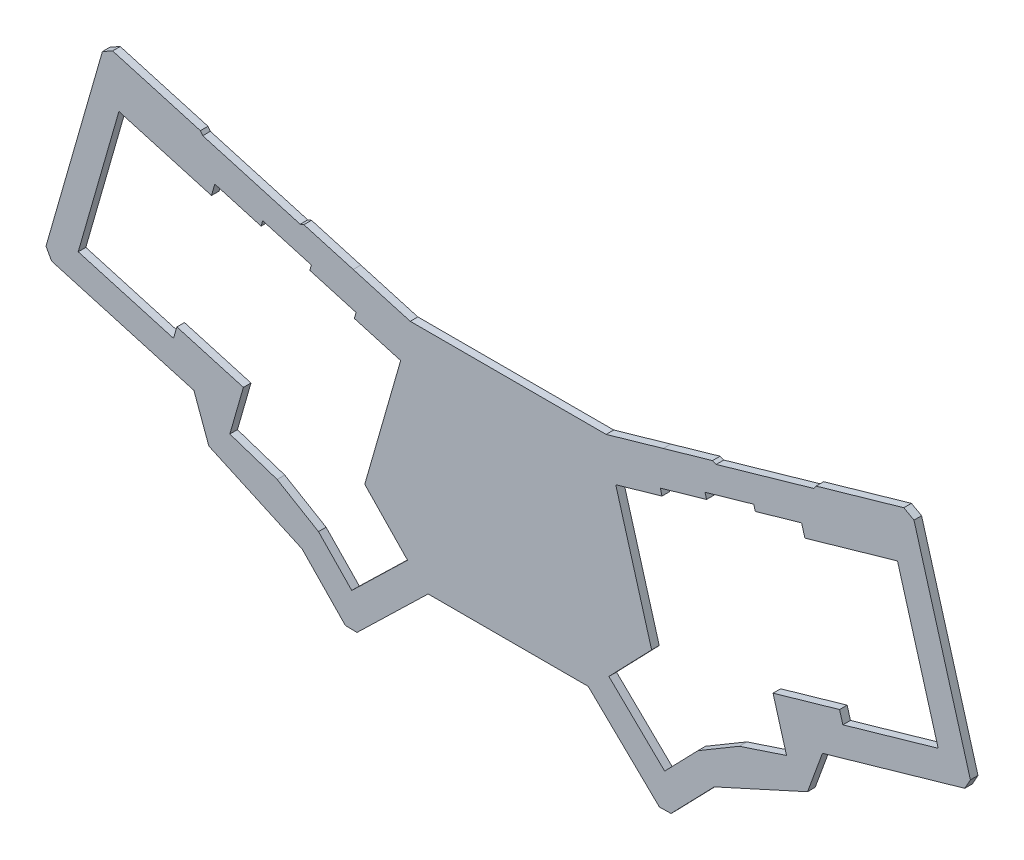
SolidWorks part; units mm, degrees
ref_plane "Plan de face" through (0, 0, 0) normal (0, 0, 1) x (1, 0, 0)
ref_plane "Plan de dessus" through (0, 0, 0) normal (0, 1, 0) x (1, 0, 0)
ref_plane "Plan de droite" through (0, 0, 0) normal (1, 0, 0) x (0, 0, -1)
sketch "Esquisse1" plane through (0, 0, 0) normal (0, 0, 1) x (1, 0, 0)
  line L0 (-121.6461, -32.0475) -> (-108.1875, -28.1884) construction
  line L1 (-108.1875, -28.1884) -> (-104.3283, -41.647) construction
  line L2 (-104.3283, -41.647) -> (-117.7869, -45.5062) construction
  line L3 (-117.7869, -45.5062) -> (-121.6461, -32.0475) construction
  line L4 (-100.1763, -37.9855) -> (-104.0355, -24.5269) construction
  line L5 (-104.0355, -24.5269) -> (-90.5769, -20.6677) construction
  line L6 (-90.5769, -20.6677) -> (-86.7177, -34.1263) construction
  line L7 (-86.7177, -34.1263) -> (-100.1763, -37.9855) construction
  line L8 (-82.5657, -30.4649) -> (-86.4249, -17.0063) construction
  line L9 (-86.4249, -17.0063) -> (-72.9663, -13.1471) construction
  line L10 (-72.9663, -13.1471) -> (-69.1071, -26.6057) construction
  line L11 (-69.1071, -26.6057) -> (-82.5657, -30.4649) construction
  line L12 (-63.6458, -27.5106) -> (-67.505, -14.0519) construction
  line L13 (-67.505, -14.0519) -> (-54.0463, -10.1927) construction
  line L14 (-54.0463, -10.1927) -> (-50.1872, -23.6514) construction
  line L15 (-50.1872, -23.6514) -> (-63.6458, -27.5106) construction
  line L16 (-44.0711, -26.8394) -> (-47.9303, -13.3808) construction
  line L17 (-47.9303, -13.3808) -> (-34.4717, -9.5216) construction
  line L18 (-34.4717, -9.5216) -> (-30.6125, -22.9802) construction
  line L19 (-30.6125, -22.9802) -> (-44.0711, -26.8394) construction
  line L20 (-25.8054, -21.6018) -> (-29.6646, -8.1432) construction
  line L21 (-29.6646, -8.1432) -> (-16.206, -4.284) construction
  line L22 (-16.206, -4.284) -> (-12.3468, -17.7426) construction
  line L23 (-12.3468, -17.7426) -> (-25.8054, -21.6018) construction
  line L24 (-116.4086, -50.3128) -> (-102.95, -46.4536) construction
  line L25 (-102.95, -46.4536) -> (-99.0908, -59.9122) construction
  line L26 (-99.0908, -59.9122) -> (-112.5494, -63.7714) construction
  line L27 (-112.5494, -63.7714) -> (-116.4086, -50.3128) construction
  line L28 (-98.798, -42.7922) -> (-85.3394, -38.933) construction
  line L29 (-85.3394, -38.933) -> (-81.4802, -52.3916) construction
  line L30 (-81.4802, -52.3916) -> (-94.9388, -56.2508) construction
  line L31 (-94.9388, -56.2508) -> (-98.798, -42.7922) construction
  line L32 (-81.1874, -35.2715) -> (-67.7288, -31.4123) construction
  line L33 (-67.7288, -31.4123) -> (-63.8696, -44.8709) construction
  line L34 (-63.8696, -44.8709) -> (-77.3282, -48.7301) construction
  line L35 (-77.3282, -48.7301) -> (-81.1874, -35.2715) construction
  line L36 (-62.2675, -32.3172) -> (-48.8089, -28.458) construction
  line L37 (-48.8089, -28.458) -> (-44.9497, -41.9166) construction
  line L38 (-44.9497, -41.9166) -> (-58.4083, -45.7758) construction
  line L39 (-58.4083, -45.7758) -> (-62.2675, -32.3172) construction
  line L40 (-42.6928, -31.646) -> (-29.2342, -27.7869) construction
  line L41 (-29.2342, -27.7869) -> (-25.375, -41.2455) construction
  line L42 (-25.375, -41.2455) -> (-38.8336, -45.1047) construction
  line L43 (-38.8336, -45.1047) -> (-42.6928, -31.646) construction
  line L44 (-24.4271, -26.4084) -> (-10.9685, -22.5492) construction
  line L45 (-10.9685, -22.5492) -> (-7.1093, -36.0078) construction
  line L46 (-7.1093, -36.0078) -> (-20.5679, -39.867) construction
  line L47 (-20.5679, -39.867) -> (-24.4271, -26.4084) construction
  line L48 (-19.1896, -44.6737) -> (-5.731, -40.8145) construction
  line L49 (-5.731, -40.8145) -> (-1.8718, -54.2731) construction
  line L50 (-1.8718, -54.2731) -> (-15.3304, -58.1323) construction
  line L51 (-15.3304, -58.1323) -> (-19.1896, -44.6737) construction
  line L52 (-37.4554, -49.9113) -> (-23.9967, -46.0521) construction
  line L53 (-23.9967, -46.0521) -> (-20.1376, -59.5107) construction
  line L54 (-20.1376, -59.5107) -> (-33.5962, -63.3699) construction
  line L55 (-33.5962, -63.3699) -> (-37.4554, -49.9113) construction
  line L56 (-57.03, -50.5825) -> (-43.5714, -46.7233) construction
  line L57 (-43.5714, -46.7233) -> (-39.7122, -60.1819) construction
  line L58 (-39.7122, -60.1819) -> (-53.1708, -64.0411) construction
  line L59 (-53.1708, -64.0411) -> (-57.03, -50.5825) construction
  line L60 (-75.9499, -53.5368) -> (-62.4913, -49.6776) construction
  line L61 (-62.4913, -49.6776) -> (-58.6321, -63.1362) construction
  line L62 (-58.6321, -63.1362) -> (-72.0908, -66.9954) construction
  line L63 (-72.0908, -66.9954) -> (-75.9499, -53.5368) construction
  line L64 (-93.5605, -61.0574) -> (-80.1019, -57.1982) construction
  line L65 (-80.1019, -57.1982) -> (-76.2427, -70.6569) construction
  line L66 (-76.2427, -70.6569) -> (-89.7013, -74.516) construction
  line L67 (-89.7013, -74.516) -> (-93.5605, -61.0574) construction
  line L68 (-111.1711, -68.5781) -> (-97.7125, -64.7189) construction
  line L69 (-97.7125, -64.7189) -> (-93.8533, -78.1775) construction
  line L70 (-93.8533, -78.1775) -> (-107.3119, -82.0367) construction
  line L71 (-107.3119, -82.0367) -> (-111.1711, -68.5781) construction
  line L72 (-79.0181, -77.3048) -> (-65.5595, -73.4456) construction
  line L73 (-65.5595, -73.4456) -> (-61.7003, -86.9042) construction
  line L74 (-61.7003, -86.9042) -> (-75.1589, -90.7634) construction
  line L75 (-75.1589, -90.7634) -> (-79.0181, -77.3048) construction
  line L76 (-99.4001, -88.1351) -> (-87.3916, -80.9362)
  line L77 (-87.3916, -80.9362) -> (-80.1927, -92.9448)
  line L78 (-80.1927, -92.9448) -> (-92.2012, -100.1436)
  line L79 (-92.2012, -100.1436) -> (-99.4001, -88.1351)
  line L80 (-120.0498, -100.4367) -> (-110.317, -90.3719)
  line L81 (-110.317, -90.3719) -> (-100.2522, -100.1047)
  line L82 (-100.2522, -100.1047) -> (-109.985, -110.1695)
  line L83 (-109.985, -110.1695) -> (-120.0498, -100.4367)
  line L86 (0.634, -55.7756) -> (-52.9527, -71.1413) construction
  line L89 (-59.2205, -88.2424) -> (-52.9527, -71.1413) construction
  line L96 (-93.4066, -103.0586) -> (-59.4637, -88.3612) construction
  line L97 (-105.418, -115.2057) -> (-93.9754, -103.3509) construction
  line L98 (-126.5332, -96.9919) -> (-107.5003, -115.385) construction
  line L99 (-167.7972, -50.1766) -> (-183.2082, -64.014) construction
  line L100 (-106.3822, -25.4572) -> (-123.6848, -30.4187) construction
  line L101 (-72.1178, -10.6906) -> (-88.4663, -15.3784) construction
  line L102 (-53.2337, -7.6163) -> (-70.5393, -12.5786) construction
  line L103 (-33.6604, -6.9452) -> (-50.9661, -11.9075) construction
  line L104 (-15.3965, -1.7081) -> (-31.745, -6.396) construction
  line L105 (0.5403, -55.2132) -> (-14.6896, -2.0999) construction
  line L106 (-16.199, -60.6113) -> (0.1495, -55.9235) construction
  line L107 (-52.7198, -71.0835) -> (-18.1144, -61.1606) construction
  line L108 (-59.1184, -88.0534) -> (-52.9674, -71.2752) construction
  line L109 (-183.2082, -64.014) -> (-173.1824, -64.9357) construction
  line L113 (-102.2678, -134.438) -> (-84.7238, -116.3191) construction
  line L114 (-84.7238, -116.3191) -> (-47.2969, -99.2981) construction
  line L115 (-47.2969, -99.2981) -> (-41.4917, -83.4594) construction
  line L116 (14.3812, -67.4381) -> (-41.4917, -83.4594) construction
  line L117 (17.8093, -61.2536) -> (-5.1371, 18.7701) construction
  line L122 (-11.3217, 22.1985) -> (-107.4545, -5.3614) construction
  line L129 (-167.7953, -27.6055) -> (-167.7953, -64.7189) construction
  line L130 (-242.0685, -103.8419) -> (-276.37, -88.2424) construction
  line L131 (-229.5108, -116.8112) -> (-242.0685, -103.8419) construction
  line L138 (-208.9328, -96.8551) -> (-229.5108, -116.8112) construction
  line L139 (-225.5107, -79.6567) -> (-208.9328, -96.8551) construction
  line L140 (-109.3352, -134.5492) -> (-102.2678, -134.438) construction
  line L142 (-5.1371, 18.7701) -> (-11.3217, 22.1985) construction
  line L143 (-211.4691, -30.6868) -> (-225.5107, -79.6567) construction
  line L147 (-114.18, -7.2899) -> (-107.4545, -5.3614) construction
  line L148 (-114.18, -7.2899) -> (-123.7936, -10.0465) construction
  line L154 (-118.7579, -16.9241) -> (-12.0005, 13.6817) construction
  line L155 (-131.531, -101.8802) -> (-105.9239, -126.7133) construction
  line L156 (-105.9239, -126.7133) -> (-89.4162, -109.6646) construction
  line L157 (-128.0696, -96.8789) -> (-106.0575, -118.2258)
  line L158 (-106.0575, -118.2258) -> (-92.9354, -104.6737)
  line L161 (1.8709, -56.4612) -> (-35.7408, -67.2462)
  line L162 (1.8709, -56.4612) -> (-14.1861, -0.4639)
  line L163 (-14.1861, -0.4639) -> (-50.7166, -10.9388)
  line L164 (-50.7166, -10.9388) -> (-52.026, -6.3725)
  line L165 (-52.026, -6.3725) -> (-70.2913, -11.61)
  line L166 (-70.2913, -11.61) -> (-70.911, -9.4488)
  line L167 (-70.911, -9.4488) -> (-90.1377, -14.9608)
  line L168 (-90.1377, -14.9608) -> (-89.5177, -17.1231)
  line L169 (-89.5177, -17.1231) -> (-107.783, -22.3606)
  line L170 (-107.783, -22.3606) -> (-107.0938, -24.7639)
  line L171 (-107.0938, -24.7639) -> (-125.3583, -30.0011)
  line L172 (-125.3583, -30.0011) -> (-111.2001, -79.378)
  line L173 (-111.2001, -79.378) -> (-127.3777, -96.1611)
  line L174 (-89.4162, -109.6646) -> (-53.6562, -93.4017) construction
  line L175 (-53.6562, -93.4017) -> (-47.6042, -76.8897) construction
  line L176 (9.2923, -60.5749) -> (-47.6042, -76.8897) construction
  line L177 (9.2923, -60.5749) -> (-12.0005, 13.6817) construction
  line L178 (-229.7336, -25.4495) -> (-211.4691, -30.6868) construction
  line L179 (-229.0444, -23.0462) -> (-229.7336, -25.4495) construction
  line L180 (-173.1824, -64.9357) -> (-167.7972, -60.1004) construction
  line L181 (-247.3097, -17.8087) -> (-229.0444, -23.0462) construction
  line L185 (17.8093, -61.2536) -> (14.3812, -67.4381) construction
  line L186 (-183.2987, -65.7677) -> (-173.2729, -66.6895) construction
  line L187 (-173.2729, -66.6895) -> (-167.8052, -74.7882) construction
  line L190 (-246.6897, -15.6465) -> (-247.3097, -17.8087) construction
  line L191 (-263.9939, -10.6857) -> (-246.6897, -15.6465) construction
  line L192 (-264.6136, -12.8469) -> (-263.9939, -10.6857) construction
  line L193 (-282.8789, -7.6094) -> (-264.6136, -12.8469) construction
  line L194 (-284.1883, -12.1757) -> (-282.8789, -7.6094) construction
  line L195 (-320.7188, -1.7008) -> (-284.1883, -12.1757) construction
  line L196 (-336.2245, -55.7756) -> (-320.7188, -1.7008) construction
  line L197 (-183.2987, -65.7677) -> (-167.8052, -88.0782) construction
  line L198 (-181.8414, -71.5322) -> (-174.8684, -81.0171) construction
  line L199 (-174.8684, -81.0171) -> (-178.3549, -83.9622) construction
  line L200 (-344.8828, -60.5749) -> (-323.5901, 13.6817) construction
  line L201 (-344.8828, -60.5749) -> (-287.9863, -76.8897) construction
  line L202 (-281.9343, -93.4017) -> (-287.9863, -76.8897) construction
  line L203 (-246.1743, -109.6646) -> (-281.9343, -93.4017) construction
  line L204 (-224.3904, -79.378) -> (-208.2128, -96.1611)
  line L205 (-210.2322, -30.0011) -> (-224.3904, -79.378)
  line L206 (-228.4967, -24.7639) -> (-210.2322, -30.0011)
  line L207 (-227.8075, -22.3606) -> (-228.4967, -24.7639)
  line L208 (-246.0728, -17.1231) -> (-227.8075, -22.3606)
  line L209 (-245.4528, -14.9608) -> (-246.0728, -17.1231)
  line L210 (-264.6796, -9.4488) -> (-245.4528, -14.9608)
  line L211 (-265.2993, -11.61) -> (-264.6796, -9.4488)
  line L212 (-283.5645, -6.3725) -> (-265.2993, -11.61)
  line L213 (-284.8739, -10.9388) -> (-283.5645, -6.3725)
  line L217 (0.634, -55.7756) -> (-14.8717, -1.7008) construction
  line L220 (-14.8717, -1.7008) -> (-51.4022, -12.1757) construction
  line L221 (-51.4022, -12.1757) -> (-52.7116, -7.6094) construction
  line L222 (-52.7116, -7.6094) -> (-70.9769, -12.8469) construction
  line L223 (-70.9769, -12.8469) -> (-71.5966, -10.6857) construction
  line L224 (-71.5966, -10.6857) -> (-88.9008, -15.6465) construction
  line L225 (-88.9008, -15.6465) -> (-88.2808, -17.8087) construction
  line L226 (-88.2808, -17.8087) -> (-106.5461, -23.0462) construction
  line L227 (-106.5461, -23.0462) -> (-105.8569, -25.4495) construction
  line L228 (-105.8569, -25.4495) -> (-124.1214, -30.6868) construction
  line L231 (-124.1214, -30.6868) -> (-110.0799, -79.6567) construction
  line L232 (-110.0799, -79.6567) -> (-126.6577, -96.8551) construction
  line L233 (-126.6577, -96.8551) -> (-106.0797, -116.8112) construction
  line L234 (-106.0797, -116.8112) -> (-93.522, -103.8419) construction
  line L235 (-93.522, -103.8419) -> (-59.2205, -88.2424) construction
  line L236 (-321.4044, -0.4639) -> (-284.8739, -10.9388)
  line L237 (-337.4614, -56.4612) -> (-321.4044, -0.4639)
  line L238 (-337.4614, -56.4612) -> (-299.8497, -67.2462)
  line L241 (-229.5331, -118.2258) -> (-242.6551, -104.6737)
  line L242 (-208.2366, -97.573) -> (-229.5331, -118.2258)
  line L243 (-229.6666, -126.7133) -> (-246.1743, -109.6646) construction
  line L244 (-204.0596, -101.8802) -> (-229.6666, -126.7133) construction
  line L245 (-331.2803, 15.8863) -> (-208.2299, -19.3904) construction
  line L246 (-178.3549, -83.9622) -> (-185.8788, -75.0552) construction
  line L247 (-185.8788, -75.0552) -> (-181.8414, -71.5322) construction
  line L248 (-176.7625, -46.6332) -> (-185.5498, -54.5291) construction
  line L249 (-185.5498, -54.5291) -> (-181.1562, -59.4188) construction
  line L250 (-181.1562, -59.4188) -> (-172.3689, -51.5229) construction
  line L251 (-276.4721, -88.0534) -> (-282.6232, -71.2752) construction
  line L252 (-282.8707, -71.0835) -> (-317.4761, -61.1606) construction
  line L253 (-319.3915, -60.6113) -> (-335.74, -55.9235) construction
  line L254 (-336.1309, -55.2132) -> (-320.9009, -2.0999) construction
  line L255 (-320.194, -1.7081) -> (-303.8455, -6.396) construction
  line L256 (-301.9301, -6.9452) -> (-284.6245, -11.9075) construction
  line L257 (-282.3568, -7.6163) -> (-265.0512, -12.5786) construction
  line L258 (-263.4727, -10.6906) -> (-247.1242, -15.3784) construction
  line L259 (-229.2083, -25.4572) -> (-211.9057, -30.4187) construction
  line L260 (-172.3689, -51.5229) -> (-176.7625, -46.6332) construction
  line L261 (-209.0573, -96.9919) -> (-228.0902, -115.385) construction
  line L262 (-230.1725, -115.2057) -> (-241.6151, -103.3509) construction
  line L263 (-242.1839, -103.0586) -> (-276.1268, -88.3612) construction
  line L264 (-276.37, -88.2424) -> (-282.6379, -71.1413) construction
  line L265 (-336.2245, -55.7756) -> (-282.6379, -71.1413) construction
  line L268 (-353.3998, -61.2536) -> (-349.9717, -67.4381) construction
  line L274 (-221.4105, -7.2899) -> (-206.0252, -11.7015) construction
  line L275 (-221.4105, -7.2899) -> (-228.136, -5.3614) construction
  line L276 (-330.4534, 18.7701) -> (-324.2688, 22.1985) construction
  line L277 (-226.2553, -134.5492) -> (-233.3227, -134.438) construction
  line L281 (-324.2688, 22.1985) -> (-228.136, -5.3614) construction
  line L282 (-353.3998, -61.2536) -> (-330.4534, 18.7701) construction
  line L283 (-349.9717, -67.4381) -> (-294.0988, -83.4594) construction
  line L284 (-288.2936, -99.2981) -> (-294.0988, -83.4594) construction
  line L285 (-250.8667, -116.3191) -> (-288.2936, -99.2981) construction
  line L286 (-233.3227, -134.438) -> (-250.8667, -116.3191) construction
  line L288 (-225.6055, -110.1695) -> (-215.5407, -100.4367) construction
  line L289 (-235.3383, -100.1047) -> (-225.6055, -110.1695) construction
  line L290 (-225.2735, -90.3719) -> (-235.3383, -100.1047) construction
  line L291 (-215.5407, -100.4367) -> (-225.2735, -90.3719) construction
  line L292 (-243.3893, -100.1436) -> (-236.1904, -88.1351) construction
  line L293 (-255.3978, -92.9448) -> (-243.3893, -100.1436) construction
  line L294 (-248.1989, -80.9362) -> (-255.3978, -92.9448) construction
  line L295 (-236.1904, -88.1351) -> (-248.1989, -80.9362) construction
  line L296 (-260.4316, -90.7634) -> (-256.5724, -77.3048) construction
  line L297 (-273.8902, -86.9042) -> (-260.4316, -90.7634) construction
  line L298 (-270.031, -73.4456) -> (-273.8902, -86.9042) construction
  line L299 (-256.5724, -77.3048) -> (-270.031, -73.4456) construction
  line L300 (-228.2786, -82.0367) -> (-224.4194, -68.5781) construction
  line L301 (-241.7372, -78.1775) -> (-228.2786, -82.0367) construction
  line L302 (-237.878, -64.7189) -> (-241.7372, -78.1775) construction
  line L303 (-224.4194, -68.5781) -> (-237.878, -64.7189) construction
  line L304 (-245.8892, -74.516) -> (-242.03, -61.0574) construction
  line L305 (-259.3478, -70.6569) -> (-245.8892, -74.516) construction
  line L306 (-255.4886, -57.1982) -> (-259.3478, -70.6569) construction
  line L307 (-242.03, -61.0574) -> (-255.4886, -57.1982) construction
  line L308 (-263.4998, -66.9954) -> (-259.6406, -53.5368) construction
  line L309 (-276.9584, -63.1362) -> (-263.4998, -66.9954) construction
  line L310 (-273.0992, -49.6776) -> (-276.9584, -63.1362) construction
  line L311 (-259.6406, -53.5368) -> (-273.0992, -49.6776) construction
  line L312 (-282.4197, -64.0411) -> (-278.5605, -50.5825) construction
  line L313 (-295.8783, -60.1819) -> (-282.4197, -64.0411) construction
  line L314 (-292.0191, -46.7233) -> (-295.8783, -60.1819) construction
  line L315 (-278.5605, -50.5825) -> (-292.0191, -46.7233) construction
  line L316 (-301.9944, -63.3699) -> (-298.1352, -49.9113) construction
  line L317 (-315.453, -59.5107) -> (-301.9944, -63.3699) construction
  line L318 (-311.5938, -46.0521) -> (-315.453, -59.5107) construction
  line L319 (-298.1352, -49.9113) -> (-311.5938, -46.0521) construction
  line L320 (-320.2601, -58.1323) -> (-316.4009, -44.6737) construction
  line L321 (-333.7187, -54.2731) -> (-320.2601, -58.1323) construction
  line L322 (-329.8595, -40.8145) -> (-333.7187, -54.2731) construction
  line L323 (-316.4009, -44.6737) -> (-329.8595, -40.8145) construction
  line L324 (-315.0226, -39.867) -> (-311.1634, -26.4084) construction
  line L325 (-328.4812, -36.0078) -> (-315.0226, -39.867) construction
  line L326 (-324.622, -22.5492) -> (-328.4812, -36.0078) construction
  line L327 (-311.1634, -26.4084) -> (-324.622, -22.5492) construction
  line L328 (-296.7569, -45.1047) -> (-292.8977, -31.646) construction
  line L329 (-310.2155, -41.2455) -> (-296.7569, -45.1047) construction
  line L330 (-306.3563, -27.7869) -> (-310.2155, -41.2455) construction
  line L331 (-292.8977, -31.646) -> (-306.3563, -27.7869) construction
  line L332 (-277.1822, -45.7758) -> (-273.323, -32.3172) construction
  line L333 (-290.6408, -41.9166) -> (-277.1822, -45.7758) construction
  line L334 (-286.7817, -28.458) -> (-290.6408, -41.9166) construction
  line L335 (-273.323, -32.3172) -> (-286.7817, -28.458) construction
  line L336 (-258.2623, -48.7301) -> (-254.4031, -35.2715) construction
  line L337 (-271.7209, -44.8709) -> (-258.2623, -48.7301) construction
  line L338 (-267.8617, -31.4123) -> (-271.7209, -44.8709) construction
  line L339 (-254.4031, -35.2715) -> (-267.8617, -31.4123) construction
  line L340 (-240.6517, -56.2508) -> (-236.7925, -42.7922) construction
  line L341 (-254.1103, -52.3916) -> (-240.6517, -56.2508) construction
  line L342 (-250.2511, -38.933) -> (-254.1103, -52.3916) construction
  line L343 (-236.7925, -42.7922) -> (-250.2511, -38.933) construction
  line L344 (-223.0411, -63.7714) -> (-219.1819, -50.3128) construction
  line L345 (-236.4997, -59.9122) -> (-223.0411, -63.7714) construction
  line L346 (-232.6405, -46.4536) -> (-236.4997, -59.9122) construction
  line L347 (-219.1819, -50.3128) -> (-232.6405, -46.4536) construction
  line L348 (-323.2438, -17.7426) -> (-309.7851, -21.6018) construction
  line L349 (-319.3846, -4.284) -> (-323.2438, -17.7426) construction
  line L350 (-305.926, -8.1432) -> (-319.3846, -4.284) construction
  line L351 (-309.7851, -21.6018) -> (-305.926, -8.1432) construction
  line L352 (-304.978, -22.9802) -> (-291.5194, -26.8394) construction
  line L353 (-301.1188, -9.5216) -> (-304.978, -22.9802) construction
  line L354 (-287.6602, -13.3808) -> (-301.1188, -9.5216) construction
  line L355 (-291.5194, -26.8394) -> (-287.6602, -13.3808) construction
  line L356 (-285.4034, -23.6514) -> (-271.9448, -27.5106) construction
  line L357 (-281.5442, -10.1927) -> (-285.4034, -23.6514) construction
  line L358 (-268.0856, -14.0519) -> (-281.5442, -10.1927) construction
  line L359 (-271.9448, -27.5106) -> (-268.0856, -14.0519) construction
  line L360 (-266.4834, -26.6057) -> (-253.0248, -30.4649) construction
  line L361 (-262.6242, -13.1471) -> (-266.4834, -26.6057) construction
  line L362 (-249.1656, -17.0063) -> (-262.6242, -13.1471) construction
  line L363 (-253.0248, -30.4649) -> (-249.1656, -17.0063) construction
  line L364 (-248.8728, -34.1263) -> (-235.4142, -37.9855) construction
  line L365 (-245.0136, -20.6677) -> (-248.8728, -34.1263) construction
  line L366 (-231.555, -24.5269) -> (-245.0136, -20.6677) construction
  line L367 (-235.4142, -37.9855) -> (-231.555, -24.5269) construction
  line L368 (-217.8036, -45.5062) -> (-213.9444, -32.0475) construction
  line L369 (-231.2622, -41.647) -> (-217.8036, -45.5062) construction
  line L370 (-227.4031, -28.1884) -> (-231.2622, -41.647) construction
  line L371 (-213.9444, -32.0475) -> (-227.4031, -28.1884) construction
  line L372 (-226.2553, -134.5492) -> (-194.0347, -103.3509) construction
  line L373 (-109.3352, -134.5492) -> (-141.5559, -103.3509) construction
  line L374 (-141.5559, -103.3509) -> (-194.0347, -103.3509) construction
  line L375 (-167.7972, -50.1766) -> (-152.3861, -64.014) construction
  line L376 (-162.4119, -64.9357) -> (-167.7972, -60.1004) construction
  line L377 (-162.3376, -66.6895) -> (-167.8052, -74.7882) construction
  line L378 (-152.3118, -65.7677) -> (-167.8052, -88.0782) construction
  line L379 (-163.2254, -51.5229) -> (-158.8318, -46.6332) construction
  line L380 (-154.4381, -59.4188) -> (-163.2254, -51.5229) construction
  line L381 (-150.0445, -54.5291) -> (-154.4381, -59.4188) construction
  line L382 (-158.8318, -46.6332) -> (-150.0445, -54.5291) construction
  line L383 (-149.7316, -75.0552) -> (-153.7691, -71.5322) construction
  line L384 (-157.2555, -83.9622) -> (-149.7316, -75.0552) construction
  line L385 (-160.742, -81.0171) -> (-157.2555, -83.9622) construction
  line L386 (-153.7691, -71.5322) -> (-160.742, -81.0171) construction
  line L387 (-152.3118, -65.7677) -> (-162.3376, -66.6895) construction
  line L388 (-152.3861, -64.014) -> (-162.4119, -64.9357) construction
  line L389 (-206.0252, -11.7015) -> (-129.5654, -11.7015) construction
  line L390 (-119.0708, -62.7964) -> (-130.6498, -22.4155) construction
  line L391 (-123.5545, -47.16) -> (-127.4136, -33.7014) construction
  line L392 (-120.442, -65.2702) -> (-138.2688, -70.3819) construction
  line L393 (-140.7426, -69.0107) -> (-154.4194, -21.3141) construction
  line L394 (-167.1758, -11.7015) -> (-206.0252, -11.7015) construction
  line L395 (-154.4194, -21.3141) -> (-167.1758, -11.7015) construction
  line L396 (-123.7936, -10.0465) -> (-130.6498, -22.4155) construction
  line L397 (-138.2688, -70.3819) -> (-140.7426, -69.0107) construction
  line L398 (-119.0708, -62.7964) -> (-120.442, -65.2702) construction
  line L399 (-129.5654, -11.7015) -> (-123.7936, -10.0465) construction
  line L400 (-165.8487, -12.7015) -> (-206.1657, -12.7015) construction
  line L401 (-221.6861, -8.2511) -> (-206.1657, -12.7015) construction
  line L402 (-221.6861, -8.2511) -> (-228.4116, -6.3226) construction
  line L403 (-324.1462, 21.1231) -> (-228.4116, -6.3226) construction
  line L404 (-329.6063, 18.0963) -> (-324.1462, 21.1231) construction
  line L405 (-352.3244, -61.1311) -> (-329.6063, 18.0963) construction
  line L406 (-352.3244, -61.1311) -> (-349.2979, -66.591) construction
  line L407 (-349.2979, -66.591) -> (-293.3347, -82.6382) construction
  line L408 (-287.4987, -98.561) -> (-293.3347, -82.6382) construction
  line L409 (-250.2802, -115.4872) -> (-287.4987, -98.561) construction
  line L410 (-232.8926, -133.4446) -> (-250.2802, -115.4872) construction
  line L411 (-226.6535, -133.5428) -> (-232.8926, -133.4446) construction
  line L412 (-226.6535, -133.5428) -> (-194.4395, -102.3509) construction
  line L413 (-141.1511, -102.3509) -> (-194.4395, -102.3509) construction
  line L414 (-108.937, -133.5428) -> (-141.1511, -102.3509) construction
  line L415 (-108.937, -133.5428) -> (-102.6979, -133.4446) construction
  line L416 (-102.6979, -133.4446) -> (-85.3104, -115.4872) construction
  line L417 (-85.3104, -115.4872) -> (-48.0918, -98.561) construction
  line L418 (-48.0918, -98.561) -> (-42.2558, -82.6382) construction
  line L419 (13.7074, -66.591) -> (-42.2558, -82.6382) construction
  line L420 (16.7339, -61.1311) -> (13.7074, -66.591) construction
  line L421 (16.7339, -61.1311) -> (-5.9842, 18.0963) construction
  line L422 (-5.9842, 18.0963) -> (-11.4443, 21.1231) construction
  line L423 (-11.4443, 21.1231) -> (-107.1789, -6.3226) construction
  line L424 (-113.9044, -8.2511) -> (-107.1789, -6.3226) construction
  line L425 (-113.9044, -8.2511) -> (-124.4792, -11.2834) construction
  line L426 (-167.1758, -12.7015) -> (-206.1657, -12.7015) construction
  line L427 (-113.9044, -8.2511) -> (-123.5179, -11.0078) construction
  line L428 (-165.8487, -12.7015) -> (-154.4194, -21.3141) construction
  line L429 (-130.6498, -22.4155) -> (-124.4792, -11.2834) construction
  line L430 (-208.2366, -97.573) -> (-207.4919, -96.8551)
  line L431 (-207.4919, -96.8551) -> (-208.2128, -96.1611)
  line L432 (-127.3777, -96.1611) -> (-128.0696, -96.8789)
  line L433 (-221.9618, -9.2124) -> (-206.3062, -13.7015) construction
  line L434 (-166.1833, -13.7015) -> (-206.3062, -13.7015) construction
  line L435 (-166.1833, -13.7015) -> (-155.2884, -21.9114) construction
  line L436 (-141.5897, -69.6845) -> (-155.2884, -21.9114) construction
  line L437 (-138.3914, -71.4574) -> (-141.5897, -69.6845) construction
  line L438 (-119.7682, -66.1172) -> (-138.3914, -71.4574) construction
  line L439 (-117.9954, -62.9189) -> (-119.7682, -66.1172) construction
  line L440 (-117.9954, -62.9189) -> (-129.5744, -22.538) construction
  line L441 (-129.5744, -22.538) -> (-123.8054, -12.1305) construction
  line L442 (-113.6287, -9.2124) -> (-123.8054, -12.1305) construction
  line L443 (-113.6287, -9.2124) -> (-106.9033, -7.2839) construction
  line L444 (-11.5669, 20.0477) -> (-106.9033, -7.2839) construction
  line L445 (-6.8313, 17.4225) -> (-11.5669, 20.0477) construction
  line L446 (15.6584, -61.0086) -> (-6.8313, 17.4225) construction
  line L447 (15.6584, -61.0086) -> (13.0336, -65.7439) construction
  line L448 (13.0336, -65.7439) -> (-43.0198, -81.817) construction
  line L449 (-48.8867, -97.824) -> (-43.0198, -81.817) construction
  line L450 (-85.8969, -114.6554) -> (-48.8867, -97.824) construction
  line L451 (-103.128, -132.4513) -> (-85.8969, -114.6554) construction
  line L452 (-108.5388, -132.5364) -> (-103.128, -132.4513) construction
  line L453 (-108.5388, -132.5364) -> (-140.7463, -101.3509) construction
  line L454 (-140.7463, -101.3509) -> (-194.8443, -101.3509) construction
  line L455 (-227.0517, -132.5364) -> (-194.8443, -101.3509) construction
  line L456 (-227.0517, -132.5364) -> (-232.4625, -132.4513) construction
  line L457 (-232.4625, -132.4513) -> (-249.6936, -114.6554) construction
  line L458 (-249.6936, -114.6554) -> (-286.7038, -97.824) construction
  line L459 (-286.7038, -97.824) -> (-292.5707, -81.817) construction
  line L460 (-348.6241, -65.7439) -> (-292.5707, -81.817) construction
  line L461 (-351.2489, -61.0086) -> (-348.6241, -65.7439) construction
  line L462 (-351.2489, -61.0086) -> (-328.7592, 17.4225) construction
  line L463 (-328.7592, 17.4225) -> (-324.0237, 20.0477) construction
  line L464 (-324.0237, 20.0477) -> (-228.6872, -7.2839) construction
  line L465 (-221.9618, -9.2124) -> (-228.6872, -7.2839) construction
  line L466 (-129.1437, -14.7015) -> (-206.4468, -14.7015)
  line L467 (-222.2374, -10.1736) -> (-206.4468, -14.7015)
  line L468 (-222.2374, -10.1736) -> (-228.9628, -8.2452)
  line L469 (-323.9011, 18.9722) -> (-289.2528, 9.0391)
  line L470 (-327.9121, 16.7487) -> (-323.9011, 18.9722)
  line L471 (-350.1735, -60.886) -> (-327.9121, 16.7487)
  line L472 (-350.1735, -60.886) -> (-347.9503, -64.8968)
  line L473 (-347.9503, -64.8968) -> (-291.8066, -80.9958)
  line L474 (-285.9089, -97.0869) -> (-291.8066, -80.9958)
  line L475 (-249.1071, -113.8236) -> (-285.9089, -97.0869)
  line L476 (-232.0324, -131.4579) -> (-249.1071, -113.8236)
  line L477 (-227.4499, -131.53) -> (-232.0324, -131.4579)
  line L478 (-227.4499, -131.53) -> (-199.3802, -104.3509)
  line L479 (-140.3415, -100.3509) -> (-195.2491, -100.3509) construction
  line L480 (-108.1406, -131.53) -> (-136.2104, -104.3509)
  line L481 (-108.1406, -131.53) -> (-103.5582, -131.4579)
  line L482 (-103.5582, -131.4579) -> (-86.4835, -113.8236)
  line L483 (-86.4835, -113.8236) -> (-49.6816, -97.0869)
  line L484 (-49.6816, -97.0869) -> (-43.7839, -80.9958)
  line L485 (12.3598, -64.8968) -> (-43.7839, -80.9958)
  line L486 (14.583, -60.886) -> (12.3598, -64.8968)
  line L487 (14.583, -60.886) -> (-7.6784, 16.7487)
  line L488 (-7.6784, 16.7487) -> (-11.6894, 18.9722)
  line L489 (-11.6894, 18.9722) -> (-46.3377, 9.0391)
  line L490 (-113.3531, -10.1736) -> (-106.6277, -8.2452)
  line L491 (-113.3531, -10.1736) -> (-129.1437, -14.7015)
  line L492 (-128.499, -22.6605) -> (-123.1316, -12.9776) construction
  line L493 (-116.9199, -63.0414) -> (-128.499, -22.6605) construction
  line L494 (-116.9199, -63.0414) -> (-119.0944, -66.9643) construction
  line L495 (-119.0944, -66.9643) -> (-138.5139, -72.5328) construction
  line L496 (-138.5139, -72.5328) -> (-142.4368, -70.3583) construction
  line L497 (-142.4368, -70.3583) -> (-156.1575, -22.5087) construction
  line L498 (-166.5179, -14.7015) -> (-156.1575, -22.5087) construction
  line L499 (-166.5179, -14.7015) -> (-206.4468, -14.7015) construction
  line L500 (-113.3531, -10.1736) -> (-123.1316, -12.9776) construction
  line L501 (-132.0793, -108.3509) -> (-203.5112, -108.3509) construction
  line L502 (-140.3415, -108.3509) -> (-195.2491, -108.3509) construction
  line L503 (-92.9354, -104.6737) -> (-76.6212, -95.0127)
  line L504 (-227.4499, -131.53) -> (-195.2491, -100.3509) construction
  line L505 (-108.1406, -131.53) -> (-140.3415, -100.3509) construction
  line L506 (-76.6212, -95.0127) -> (-57.9612, -88.8254)
  line L507 (-57.9612, -88.8254) -> (-63.3014, -70.2021)
  line L508 (-37.0515, -62.6751) -> (-63.3014, -70.2021)
  line L509 (-37.0515, -62.6751) -> (-35.7408, -67.2462)
  line L510 (-298.539, -62.6751) -> (-299.8497, -67.2462)
  line L511 (-298.539, -62.6751) -> (-272.2891, -70.2021)
  line L512 (-277.6293, -88.8254) -> (-272.2891, -70.2021)
  line L513 (-258.9693, -95.0127) -> (-277.6293, -88.8254)
  line L514 (-242.6551, -104.6737) -> (-258.9693, -95.0127)
  line L515 (-66.4927, 2.2629) -> (-65.3792, -1.6212) construction
  line L516 (-85.7183, -3.2488) -> (-47.2672, 7.7746)
  line L517 (-87.1765, -2.6688) -> (-85.7183, -3.2488)
  line L518 (-289.2528, 9.0391) -> (-288.3233, 7.7746)
  line L519 (-87.1765, -2.6688) -> (-106.6277, -8.2452)
  line L520 (-46.3377, 9.0391) -> (-47.2672, 7.7746)
  line L521 (-11.6894, 18.9722) -> (-106.6277, -8.2452) construction
  line L522 (-249.8723, -3.2488) -> (-288.3233, 7.7746)
  line L523 (-248.414, -2.6688) -> (-249.8723, -3.2488)
  line L524 (-248.414, -2.6688) -> (-228.9628, -8.2452)
  line L525 (-134.1448, -106.3509) -> (-201.4457, -106.3509) construction
  line L526 (-323.9011, 18.9722) -> (-228.9628, -8.2452) construction
  line L527 (-136.2104, -104.3509) -> (-199.3802, -104.3509)
  line L528 (-132.0793, -106.3509) -> (-203.5112, -106.3509) construction
  line L530 (-134.1448, -104.3509) -> (-201.4457, -104.3509) construction
  circle A2 centre (-12.0005, 13.6817) radius 1.6 construction
  circle A3 centre (-12.0005, 13.6817) radius 3 construction
  circle A4 centre (-118.7579, -16.9241) radius 3 construction
  circle A5 centre (9.2923, -60.5749) radius 3 construction
  circle A6 centre (-53.6562, -93.4017) radius 3 construction
  circle A7 centre (-105.9239, -126.7133) radius 3 construction
  circle A8 centre (-131.531, -101.8802) radius 3 construction
  circle A10 centre (-147.4897, -45.973) radius 1.6 construction
  circle A11 centre (-323.5901, 13.6817) radius 3 construction
  circle A12 centre (-188.1008, -45.973) radius 1.6 construction
  circle A14 centre (-204.0596, -101.8802) radius 3 construction
  circle A15 centre (-229.6666, -126.7133) radius 3 construction
  circle A16 centre (-281.9343, -93.4017) radius 3 construction
  circle A17 centre (-344.8828, -60.5749) radius 3 construction
  circle A18 centre (-216.8326, -16.9241) radius 3 construction
  circle A19 centre (-323.5901, 13.6817) radius 1.6 construction
  circle A20 centre (-167.7953, -27.6055) radius 3 construction
  point P138 (-167.7953, -27.6055)
  point P139 (-6.5153, 23.5764)
  point P150 (-169.1046, -23.0392)
  point P200 (19.1875, -66.0599)
  point P203 (-141.5228, -71.3355)
  point P204 (-141.5228, 1.5705)
  point P263 (-133.4062, -12.8029)
  point P264 (-118.5195, -64.7189)
  point P283 (-140.1914, -70.9332)
  point P284 (-157.1758, -11.7015)
  point P405 (-354.778, -66.0599)
  point P406 (-329.0752, 23.5764)
  point P516 (-65.3792, -1.6212)
  dimension "D3" = 3.2
  dimension "D4" = 6
  dimension "D6" = 6
  dimension "D7" = 6
  dimension "D8" = 6
  dimension "D9" = 6
  dimension "D10" = 6
  dimension "D16" = 3.2
  dimension "D14" = 6
  dimension "D2" = 6
  dimension "D5" = 1
  dimension "D11" = 1
  dimension "D18" = 1
  dimension "D20" = 8
  dimension "D21" = 2
  dimension "D22" = 2
extrude "Boss.-Extru.1" add sketch "Esquisse1" along normal blind 3 contours L490 L491 L466 L467 L468 L469 L470 L471 L472 L473 L474 L475 L476 L477 L478 L479 L480 L481 L482 L483 L484 L485 L486 L487 L488 L489 L431 L430 L242 L241 L238 L237 L236 L213 L212 L211 L210 L209 L208 L207 L206 L205 L204 L432 L173 L172 L171 region at (-167.7952, -53.6555, 0)
sketch "Esquisse2" plane through (0, 0, 3) normal (0, 0, 1) x (1, 0, 0)
  line L0 (-167.7953, -108.3509) -> (-167.7953, -102.3509) construction
  line L1 (-132.0793, -108.3509) -> (-203.5112, -108.3509) construction
  line L2 (-168.7953, -108.3509) -> (-168.7953, -102.3509)
  line L3 (-166.7953, -108.3509) -> (-166.7953, -102.3509)
  line L4 (-163.7953, -108.3509) -> (-163.7953, -102.3509) construction
  line L5 (-164.7953, -108.3509) -> (-164.7953, -102.3509)
  line L6 (-162.7953, -108.3509) -> (-162.7953, -102.3509)
  line L7 (-159.7953, -108.3509) -> (-159.7953, -102.3509) construction
  line L8 (-160.7953, -108.3509) -> (-160.7953, -102.3509)
  line L9 (-158.7953, -108.3509) -> (-158.7953, -102.3509)
  line L10 (-155.7953, -108.3509) -> (-155.7953, -102.3509) construction
  line L11 (-156.7953, -108.3509) -> (-156.7953, -102.3509)
  line L12 (-154.7953, -108.3509) -> (-154.7953, -102.3509)
  line L13 (-151.7953, -108.3509) -> (-151.7953, -102.3509) construction
  line L14 (-152.7953, -108.3509) -> (-152.7953, -102.3509)
  line L15 (-150.7953, -108.3509) -> (-150.7953, -102.3509)
  line L16 (-147.7953, -108.3509) -> (-147.7953, -102.3509) construction
  line L17 (-148.7953, -108.3509) -> (-148.7953, -102.3509)
  line L18 (-146.7953, -108.3509) -> (-146.7953, -102.3509)
  line L19 (-171.7953, -108.3509) -> (-171.7953, -102.3509) construction
  line L20 (-172.7953, -108.3509) -> (-172.7953, -102.3509)
  line L21 (-170.7953, -108.3509) -> (-170.7953, -102.3509)
  line L22 (-175.7953, -108.3509) -> (-175.7953, -102.3509) construction
  line L23 (-176.7953, -108.3509) -> (-176.7953, -102.3509)
  line L24 (-174.7953, -108.3509) -> (-174.7953, -102.3509)
  line L25 (-179.7953, -108.3509) -> (-179.7953, -102.3509) construction
  line L26 (-180.7953, -108.3509) -> (-180.7953, -102.3509)
  line L27 (-178.7953, -108.3509) -> (-178.7953, -102.3509)
  line L28 (-183.7953, -108.3509) -> (-183.7953, -102.3509) construction
  line L29 (-184.7953, -108.3509) -> (-184.7953, -102.3509)
  line L30 (-182.7953, -108.3509) -> (-182.7953, -102.3509)
  line L31 (-187.7953, -108.3509) -> (-187.7953, -102.3509) construction
  line L32 (-188.7953, -108.3509) -> (-188.7953, -102.3509)
  line L33 (-186.7953, -108.3509) -> (-186.7953, -102.3509)
  arc A0 (-168.7953, -108.3509) -> (-166.7953, -108.3509) centre (-167.7953, -108.3509) ccw
  arc A1 (-166.7953, -102.3509) -> (-168.7953, -102.3509) centre (-167.7953, -102.3509) ccw
  arc A2 (-164.7953, -108.3509) -> (-162.7953, -108.3509) centre (-163.7953, -108.3509) ccw
  arc A3 (-162.7953, -102.3509) -> (-164.7953, -102.3509) centre (-163.7953, -102.3509) ccw
  arc A4 (-160.7953, -108.3509) -> (-158.7953, -108.3509) centre (-159.7953, -108.3509) ccw
  arc A5 (-158.7953, -102.3509) -> (-160.7953, -102.3509) centre (-159.7953, -102.3509) ccw
  arc A6 (-156.7953, -108.3509) -> (-154.7953, -108.3509) centre (-155.7953, -108.3509) ccw
  arc A7 (-154.7953, -102.3509) -> (-156.7953, -102.3509) centre (-155.7953, -102.3509) ccw
  arc A8 (-152.7953, -108.3509) -> (-150.7953, -108.3509) centre (-151.7953, -108.3509) ccw
  arc A9 (-150.7953, -102.3509) -> (-152.7953, -102.3509) centre (-151.7953, -102.3509) ccw
  arc A10 (-148.7953, -108.3509) -> (-146.7953, -108.3509) centre (-147.7953, -108.3509) ccw
  arc A11 (-146.7953, -102.3509) -> (-148.7953, -102.3509) centre (-147.7953, -102.3509) ccw
  arc A12 (-172.7953, -108.3509) -> (-170.7953, -108.3509) centre (-171.7953, -108.3509) ccw
  arc A13 (-170.7953, -102.3509) -> (-172.7953, -102.3509) centre (-171.7953, -102.3509) ccw
  arc A14 (-176.7953, -108.3509) -> (-174.7953, -108.3509) centre (-175.7953, -108.3509) ccw
  arc A15 (-174.7953, -102.3509) -> (-176.7953, -102.3509) centre (-175.7953, -102.3509) ccw
  arc A16 (-180.7953, -108.3509) -> (-178.7953, -108.3509) centre (-179.7953, -108.3509) ccw
  arc A17 (-178.7953, -102.3509) -> (-180.7953, -102.3509) centre (-179.7953, -102.3509) ccw
  arc A18 (-184.7953, -108.3509) -> (-182.7953, -108.3509) centre (-183.7953, -108.3509) ccw
  arc A19 (-182.7953, -102.3509) -> (-184.7953, -102.3509) centre (-183.7953, -102.3509) ccw
  arc A20 (-188.7953, -108.3509) -> (-186.7953, -108.3509) centre (-187.7953, -108.3509) ccw
  arc A21 (-186.7953, -102.3509) -> (-188.7953, -102.3509) centre (-187.7953, -102.3509) ccw
  point P4 (-167.7953, -105.3509)
  point P12 (-163.7953, -105.3509)
  point P19 (-159.7953, -105.3509)
  point P26 (-155.7953, -105.3509)
  point P33 (-151.7953, -105.3509)
  point P40 (-147.7953, -105.3509)
  point P47 (-171.7953, -105.3509)
  point P54 (-175.7953, -105.3509)
  point P61 (-179.7953, -105.3509)
  point P68 (-183.7953, -105.3509)
  point P75 (-187.7953, -105.3509)
  dimension "D1" = 6
  dimension "D2" = 6
